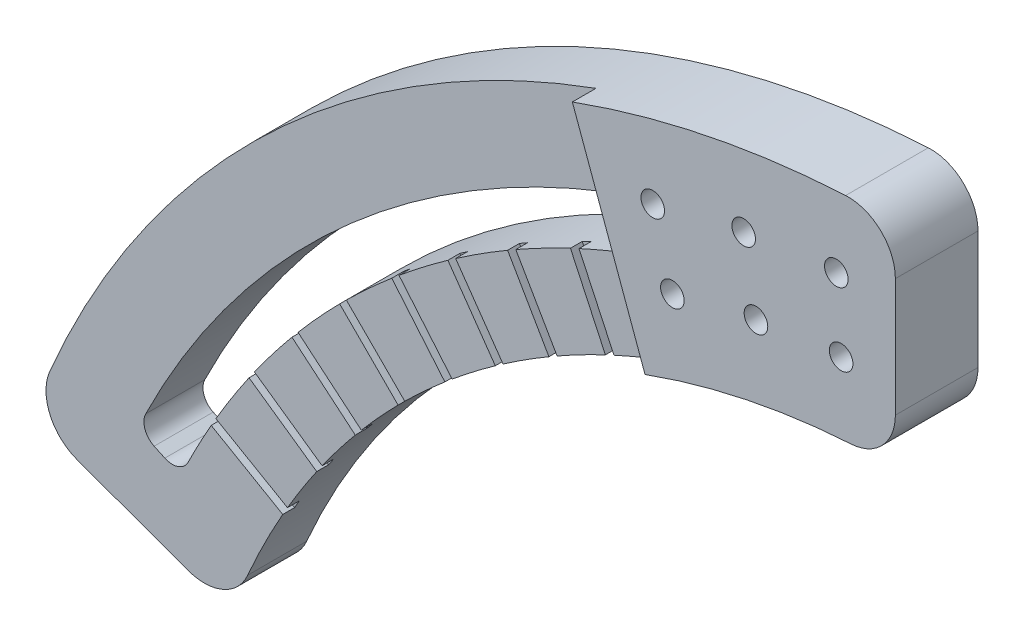
SolidWorks part; units mm, degrees
ref_plane "Front Plane" through (0, 0, 0) normal (0, 0, 1) x (1, 0, 0)
ref_plane "Top Plane" through (0, 0, 0) normal (0, 1, 0) x (1, 0, 0)
ref_plane "Right Plane" through (0, 0, 0) normal (1, 0, 0) x (0, 0, -1)
sketch "Sketch1" plane through (0, 0, 0) normal (0, 0, 1) x (1, 0, 0)
  line L0 (0, 62) -> (0, 74) construction
  line L1 (0, 0) -> (-61.6289, 28.738) construction
  line L2 (0, 68) -> (0, 74)
  line L4 (0, 65.8787) -> (0, 75.8947)
  line L5 (0, 0) -> (0, 80) construction
  line L6 (0, 0) -> (-27.3616, 75.1754) construction
  line L7 (-27.3616, 75.1754) -> (-21.2052, 58.2609)
  line L8 (-20.5532, 71.0884) -> (0, 0) construction
  line L9 (0, 0) -> (-5, 73.8309) construction
  line L10 (0, 0) -> (-75.1754, 27.3616) construction
  line L11 (-71.3177, 25.9575) -> (-61.9057, 22.5318)
  line L13 (-67.0668, 31.2738) -> (-72.5046, 33.8095) construction
  line L14 (-66.1605, 30.8511) -> (-62.5352, 29.1607)
  line L15 (-12.85, 72.8758) -> (0, 0) construction
  arc A0 (0, 68) -> (-23.2574, 63.8991) centre (0, 0) ccw
  arc A1 (0, 74) -> (-25.3095, 69.5373) centre (0, 0) ccw
  arc A2 (-4.2105, 79.8891) -> (-73.6311, 31.2803) centre (0, 0) ccw
  arc A3 (-3.7576, 61.886) -> (-56.8687, 24.6972) centre (0, 0) ccw
  arc A4 (0, 65.8787) -> (-3.7576, 61.886) centre (-4, 65.8787) cw
  arc A5 (0, 75.8947) -> (-4.2105, 79.8891) centre (-4, 75.8947) ccw
  circle A6 centre (-20.5532, 71.0884) radius 1
  circle A7 centre (-5, 73.8309) radius 1
  circle A8 centre (-18.8867, 65.3245) radius 1
  circle A9 centre (-4.5946, 67.8446) radius 1
  arc A12 (-56.8687, 24.6972) -> (-61.9057, 22.5318) centre (-60.5376, 26.2906) cw
  arc A13 (-71.3177, 25.9575) -> (-73.6311, 31.2803) centre (-69.9496, 29.7163) cw
  arc A16 (-23.5994, 64.8388) -> (-62.5352, 29.1607) centre (0, 0) ccw
  arc A19 (-24.9675, 68.5976) -> (-66.1605, 30.8511) centre (0, 0) ccw
  circle A20 centre (-12.85, 72.8758) radius 1
  circle A21 centre (-11.8081, 66.9669) radius 1
  point P8 (-58.2609, 21.2052)
  point P31 (-80, 0)
  dimension "D1" = 80
  dimension "D2" = 62
  dimension "D3" = 68
  dimension "D4" = 74
  dimension "D5" = 20
  dimension "D6" = 4
  dimension "D7" = 2
  dimension "D8" = 2
  dimension "D10" = 5
  dimension "D11" = 2
  dimension "D12" = 2
  dimension "D13" = 4
  dimension "D16" = 2
  dimension "D17" = 2
  dimension "D9" = 5
  dimension "D14" = 50
  dimension "D15" = 45
extrude "Boss-Extrude2" add sketch "Sketch1" along normal blind 5 contours L14 A1 L7 A2 A13 L11 A12 A3 A0 region at (-43.0032, 45.6935, 0)
extrude "Boss-Extrude3" add sketch "Sketch1<5>" along normal blind 7 contours A7 A1 L4 A5 A2 L7 A6 | A9 A0 L2 A1 A7 A6 L7 A8 | A9 A0 A8 L7 A3 A4 L4 region at (-12.2734, 69.6057, 0) region at (-11.4742, 63.6608, 0) region at (-13.6245, 75.4729, 0)
sketch "Sketch1<5>" plane through (0, 0, 0) normal (0, 0, 1) x (1, 0, 0) same geometry as "Sketch1"
fillet "Fillet1" radius 1.5 4 edges at (-24.9675, 68.5976, 2.5) (-23.5994, 64.8388, 2.5) (-62.5352, 29.1607, 2.5) (-66.1605, 30.8511, 2.5)
sketch "Sketch2" plane through (0, 0, 5) normal (0, 0, 1) x (1, 0, 0)
  line L0 (-27.3616, 75.1754) -> (0, 0) construction
  line L1 (0, 0) -> (-45.9401, 50.1349) construction
  line L2 (0, 0) -> (-28.738, 61.6289) construction
  line L3 (0, 0) -> (-34, 58.8897) construction
  line L4 (-26.1827, 55.2026) -> (-25.4577, 55.5407)
  line L5 (-26.1827, 55.2026) -> (-30.3954, 64.2366)
  line L6 (-25.4577, 55.5407) -> (-29.6703, 64.5747)
  line L7 (-30.3954, 64.2366) -> (-29.6703, 64.5747)
  line L8 (-30.8943, 52.7105) -> (-35.8783, 61.343)
  line L9 (-30.2015, 53.1105) -> (-35.1855, 61.743)
  line L10 (-35.8783, 61.343) -> (-35.1855, 61.743)
  line L11 (-30.8943, 52.7105) -> (-30.2015, 53.1105)
  line L12 (-35.3708, 49.8173) -> (-41.0882, 57.9826)
  line L13 (-34.7155, 50.2762) -> (-40.4328, 58.4415)
  line L14 (-41.0882, 57.9826) -> (-40.4328, 58.4415)
  line L15 (-35.3708, 49.8173) -> (-34.7155, 50.2762)
  line L16 (-39.5781, 46.545) -> (-45.9853, 54.1809)
  line L17 (-38.9652, 47.0592) -> (-45.3725, 54.6951)
  line L18 (-45.9853, 54.1809) -> (-45.3725, 54.6951)
  line L19 (-39.5781, 46.545) -> (-38.9652, 47.0592)
  line L20 (-43.4841, 42.9184) -> (-50.5325, 49.9668)
  line L21 (-42.9184, 43.4841) -> (-49.9668, 50.5325)
  line L22 (-50.5325, 49.9668) -> (-49.9668, 50.5325)
  line L23 (-43.4841, 42.9184) -> (-42.9184, 43.4841)
  line L24 (-47.0592, 38.9652) -> (-54.6951, 45.3725)
  line L25 (-46.545, 39.5781) -> (-54.1809, 45.9853)
  line L26 (-54.6951, 45.3725) -> (-54.1809, 45.9853)
  line L27 (-47.0592, 38.9652) -> (-46.545, 39.5781)
  line L28 (-50.2762, 34.7155) -> (-58.4415, 40.4328)
  line L29 (-49.8173, 35.3708) -> (-57.9826, 41.0882)
  line L30 (-58.4415, 40.4328) -> (-57.9826, 41.0882)
  line L31 (-50.2762, 34.7155) -> (-49.8173, 35.3708)
  line L32 (-53.1105, 30.2015) -> (-61.743, 35.1855)
  line L33 (-52.7105, 30.8943) -> (-61.343, 35.8783)
  line L34 (-61.743, 35.1855) -> (-61.343, 35.8783)
  line L35 (-53.1105, 30.2015) -> (-52.7105, 30.8943)
  line L40 (-55.5407, 25.4577) -> (-64.5747, 29.6703) [skipped]
  line L41 (-55.2026, 26.1827) -> (-64.2366, 30.3954) [skipped]
  line L42 (-55.5407, 25.4577) -> (-55.2026, 26.1827) [skipped]
  line L43 (-64.5747, 29.6703) -> (-64.2366, 30.3954) [skipped]
  point P49 (0, 0)
  dimension "D1" = 5
  dimension "D2" = 5
  dimension "D3" = 0.4
  dimension "D4" = 0.8
  dimension "D6" = 10
  dimension "D5" = 9
extrude "Cut-Extrude1" cut sketch "Sketch2" against normal blind 1
